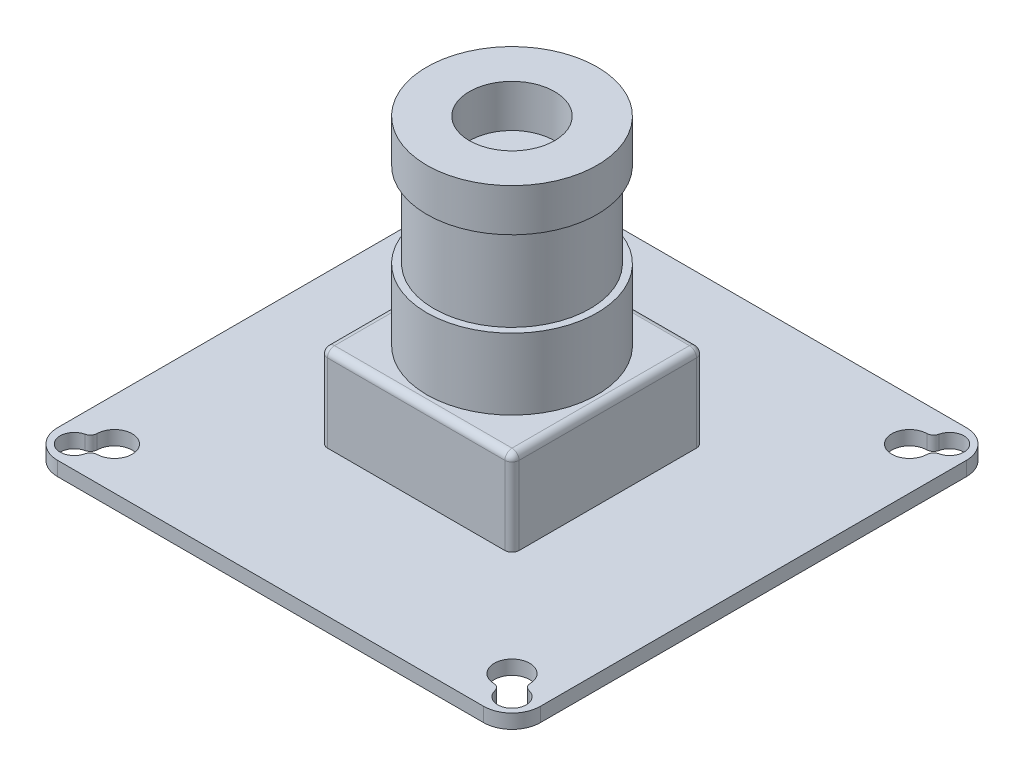
SolidWorks part; units mm, degrees
ref_plane "Front Plane" through (0, 0, 0) normal (0, 0, 1) x (1, 0, 0)
ref_plane "Top Plane" through (0, 0, 0) normal (0, 1, 0) x (1, 0, 0)
ref_plane "Right Plane" through (0, 0, 0) normal (1, 0, 0) x (0, 0, -1)
sketch "Sketch2" plane through (0, 0, 0) normal (0, 1, 0) x (1, 0, 0)
  line L1 (-17, -17) -> (17, -17)
  line L2 (-17, -17) -> (-17, 17)
  line L3 (-17, 17) -> (17, 17)
  line L4 (17, -17) -> (17, 17)
  line L5 (-17, -17) -> (17, 17) construction
  line L6 (-17, 17) -> (17, -17) construction
  point P0 (0, 0)
  dimension "D1" = 34
extrude "Boss-Extrude2" add sketch "Sketch2" along normal blind 1
fillet "Fillet1" radius 2 4 edges at (-17, 0.5, -17) (17, 0.5, -17) (-17, 0.5, 17) (17, 0.5, 17)
sketch "Sketch3" plane through (0, 1, 0) normal (0, 1, 0) x (1, 0, 0)
  line L1 (-6.75, -6.75) -> (6.75, -6.75)
  line L2 (-6.75, -6.75) -> (-6.75, 6.75)
  line L3 (-6.75, 6.75) -> (6.75, 6.75)
  line L4 (6.75, -6.75) -> (6.75, 6.75)
  line L5 (-6.75, -6.75) -> (6.75, 6.75) construction
  line L6 (-6.75, 6.75) -> (6.75, -6.75) construction
  point P0 (0, 0)
  dimension "D1" = 13.5
  dimension "D2" = 13.5
extrude "Boss-Extrude3" add sketch "Sketch3" along normal blind 6
sketch "Sketch4" plane through (0, 7, 0) normal (0, 1, 0) x (1, 0, 0)
  circle A0 centre (0, 0) radius 6
  dimension "D1" = 12
extrude "Boss-Extrude4" add sketch "Sketch4" along normal blind 5
fillet "Fillet2" radius 0.5 8 edges at (-6.75, 7, 0) (0, 7, -6.75) (6.75, 7, 0) (0, 7, 6.75) (-6.75, 4, -6.75) (-6.75, 4, 6.75) (6.75, 4, -6.75) (6.75, 4, 6.75)
sketch "Sketch5" plane through (0, 12, 0) normal (0, 1, 0) x (1, 0, 0)
  circle A0 centre (0, 0) radius 5.5
  circle A1 centre (0, 0) radius 6 construction
  dimension "D1" = 0.5
extrude "Boss-Extrude5" add sketch "Sketch5" along normal blind 6
sketch "Sketch6" plane through (0, 18, 0) normal (0, 1, 0) x (1, 0, 0)
  circle A0 centre (0, 0) radius 3
  circle A1 centre (0, 0) radius 6
  circle A2 centre (0, 0) radius 6 construction
  dimension "D1" = 6
extrude "Boss-Extrude6" add sketch "Sketch6" along normal blind 3
sketch "Sketch7" plane through (0, 1, 0) normal (0, 1, 0) x (1, 0, 0)
  line L0 (-14, 14) -> (-14, -14) construction
  line L1 (-14, -14) -> (14, -14) construction
  line L2 (14, -14) -> (14, 14) construction
  line L3 (14, 14) -> (-14, 14) construction
  line L4 (15, 17) -> (-15, 17) construction
  line L5 (17, -15) -> (17, 15) construction
  line L6 (14, 14) -> (15.4142, 15.4142) construction
  line L7 (-15.4142, 15.4142) -> (-14, 14) construction
  circle A0 centre (-14, 14) radius 1.25
  circle A1 centre (14, 14) radius 1.25
  circle A2 centre (14, -14) radius 1.25
  circle A3 centre (-14, -14) radius 1.25
  circle A4 centre (15.4142, 15.4142) radius 1
  circle A5 centre (15.4142, -15.4142) radius 1
  circle A6 centre (-15.4142, -15.4142) radius 1
  circle A7 centre (-15.4142, 15.4142) radius 1
  point P11 (0, 17)
  point P12 (0, 14)
  point P15 (17, 0)
  point P16 (14, 0)
  point P27 (0, 0)
  dimension "D3" = 2.5
  dimension "D6" = 2
  dimension "D1" = 28
  dimension "D2" = 28
  dimension "D4" = 135
  dimension "D5" = 2
  dimension "D7" = 4
extrude "Cut-Extrude1" cut sketch "Sketch7" against normal through all contours A6 A3 | A3 A6 | A3 A6 | A5 A2 | A2 A5 | A2 A5 | A4 A1 | A1 A4 | A1 A4 | A7 A0 | A0 A7 | A0 A7 region at (-13.9709, 1, -13.9709) region at (-14.7975, 1, -14.7975) region at (-15.4501, 1, -15.4501) region at (13.9709, 1, -13.9709) region at (14.7975, 1, -14.7975) region at (15.4501, 1, -15.4501) region at (13.9709, 1, 13.9709) region at (14.7975, 1, 14.7975) region at (15.4501, 1, 15.4501) region at (-13.9709, 1, 13.9709) region at (-14.7975, 1, 14.7975) region at (-15.4501, 1, 15.4501)
fillet "Fillet3" radius 0.5 8 edges at (15.1681, 0.5, -14.445) (14.445, 0.5, -15.1681) (14.445, 0.5, 15.1681) (15.1681, 0.5, 14.445) (-14.445, 0.5, 15.1681) (-15.1681, 0.5, 14.445) (-14.445, 0.5, -15.1681) (-15.1681, 0.5, -14.445)
